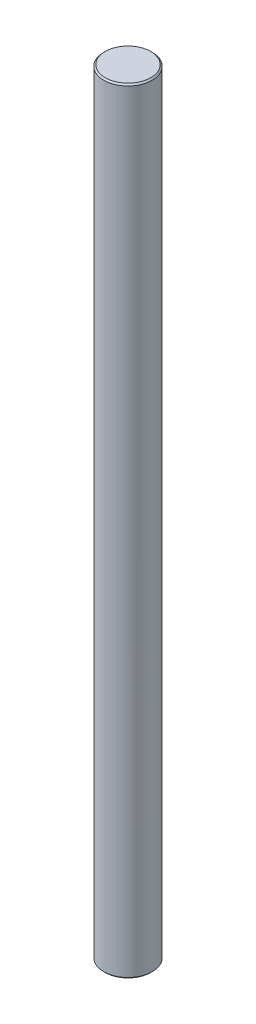
SolidWorks part; units mm, degrees
ref_plane "Front Plane" through (0, 0, 0) normal (0, 0, 1) x (1, 0, 0)
ref_plane "Top Plane" through (0, 0, 0) normal (0, 1, 0) x (1, 0, 0)
ref_plane "Right Plane" through (0, 0, 0) normal (1, 0, 0) x (0, 0, -1)
sketch "Sketch1" plane through (0, 0, 0) normal (0, 0, 1) x (1, 0, 0)
  line L1 (5, 160) -> (0, 160)
  line L2 (5, 160) -> (5, 0)
  line L3 (5, 0) -> (0, 0)
  line L4 (0, 160) -> (0, 0)
  line L5 (5, 160) -> (0, 0) construction
  line L6 (5, 0) -> (0, 160) construction
  point P0 (2.5, 80)
  dimension "D1" = 5
  dimension "D2" = 160
revolve "Revolve1" add sketch "Sketch1" angle 360 about L4
chamfer "Chamfer1" distance 0.3 angle 45 2 edges at (-5, 160, 0) (-5, 0, 0)
ref_axis "Axis1" through (0, 0.3, 0) along (0, 1, 0)
